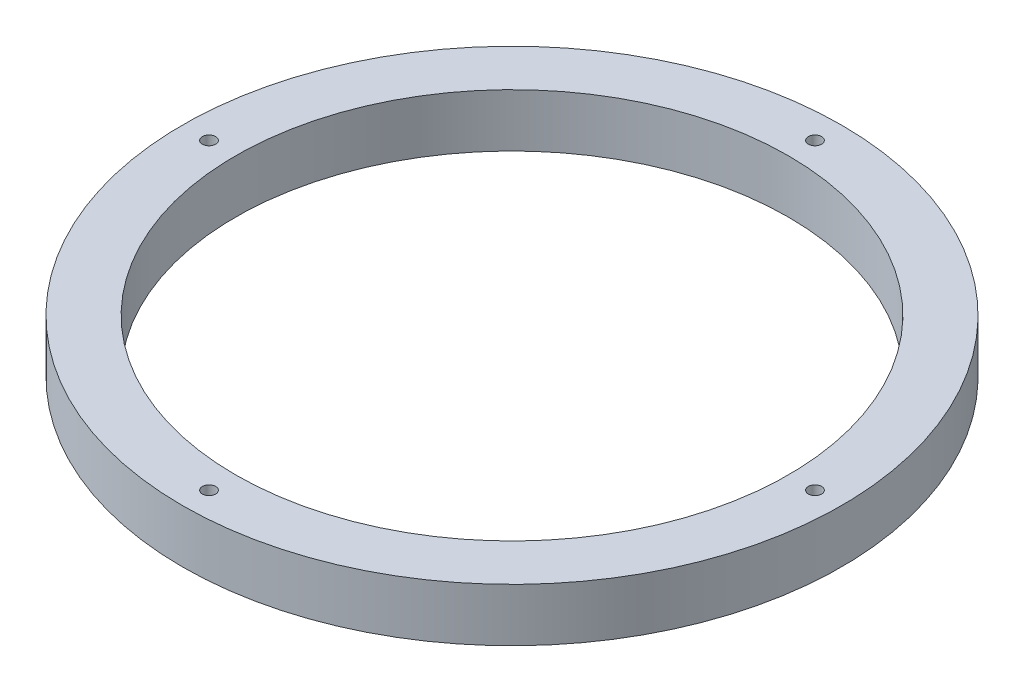
SolidWorks part; units mm, degrees
ref_plane "Front Plane" through (0, 0, 0) normal (0, 0, 1) x (1, 0, 0)
ref_plane "Top Plane" through (0, 0, 0) normal (0, 1, 0) x (1, 0, 0)
ref_plane "Right Plane" through (0, 0, 0) normal (1, 0, 0) x (0, 0, -1)
sketch "Sketch1" plane through (0, 0, 0) normal (0, 1, 0) x (1, 0, 0)
  line L0 (0, 36.195) -> (0, 0) construction
  circle A0 centre (0, 0) radius 33.02
  circle A1 centre (0, 0) radius 39.37
  circle A2 centre (0, 36.195) radius 0.7937
  circle A3 centre (36.195, 0) radius 0.7938
  circle A4 centre (0, -36.195) radius 0.7938
  circle A5 centre (-36.195, 0) radius 0.7938
  point P15 (0, 0)
  dimension "D1" = 66.04
  dimension "D2" = 78.74
  dimension "D4" = 1.5875
  dimension "D3" = 36.195
  dimension "D5" = 4
extrude "Boss-Extrude1" add sketch "Sketch1" along normal blind 6.35
